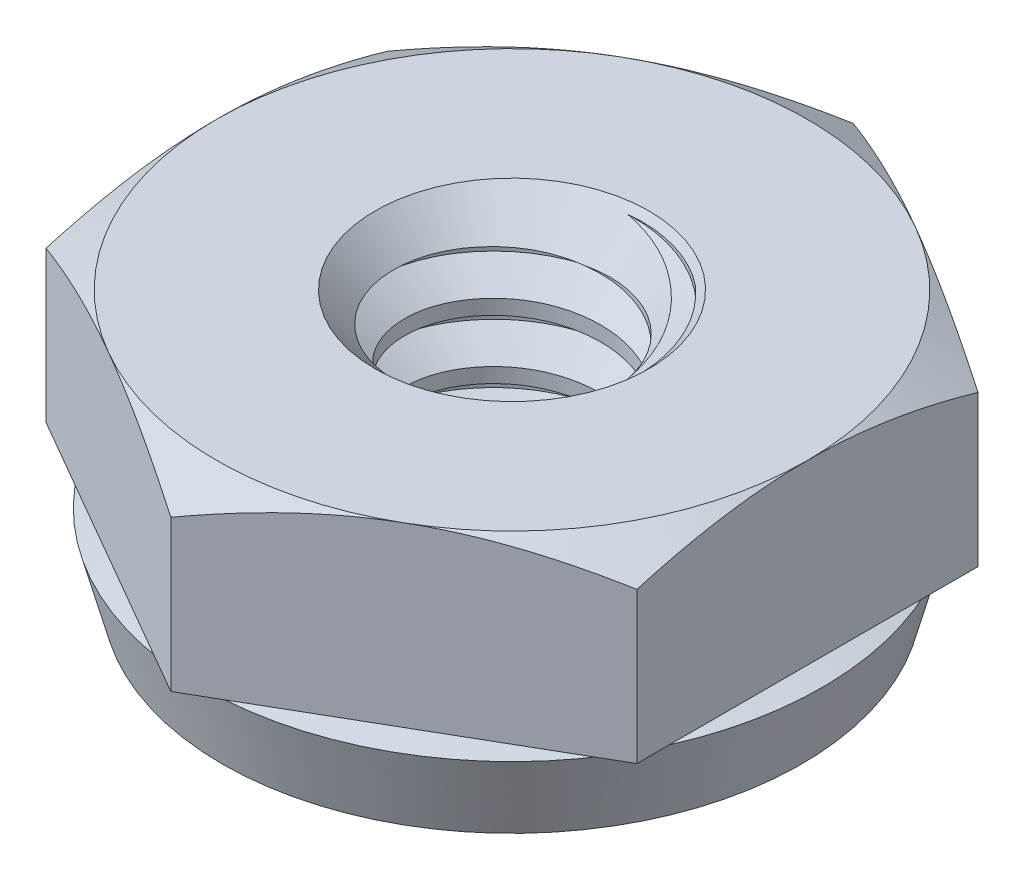
SolidWorks part; units mm, degrees
ref_plane "Front Plane" through (0, 0, 0) normal (0, 0, 1) x (1, 0, 0)
ref_plane "Top Plane" through (0, 0, 0) normal (0, 1, 0) x (1, 0, 0)
ref_plane "Right Plane" through (0, 0, 0) normal (1, 0, 0) x (0, 0, -1)
sketch "Sketch1" plane through (0, 0, 0) normal (0, 1, 0) x (1, 0, 0)
  line L1 (0, 4.5827) -> (-3.9688, 2.2914)
  line L2 (-3.9688, 2.2914) -> (-3.9688, -2.2914)
  line L3 (-3.9688, -2.2914) -> (0, -4.5827)
  line L4 (0, -4.5827) -> (3.9688, -2.2914)
  line L5 (3.9688, -2.2914) -> (3.9687, 2.2914)
  line L6 (3.9687, 2.2914) -> (0, 4.5827)
  circle A0 centre (0, 0) radius 3.9688 construction
  circle A1 centre (0, 0) radius 4.1672 construction
  point P9 (0, 4.5827)
  point P10 (0, 4.1672)
  dimension "Wd." = 7.9375
  dimension "Washer Dia." = 8.3344
extrude "Boss-Extrude1" add sketch "Sketch1" along normal blind 3.5719
sketch "Sketch4" plane through (0, 3.5719, 0) normal (0, 1, 0) x (1, 0, 0)
  circle A0 centre (0, 0) radius 1.7526
  dimension "Screw Dia." = 3.5052
sketch "Sketch5" plane through (0, 3.5719, 0) normal (0, 1, 0) x (1, 0, 0)
  circle A1 centre (0, 0) radius 1.7526
  circle A2 centre (0, 0) radius 1.7526
  point P0 (0, 1.7526)
  dimension "D1" = 0
curve "Helix/Spiral1" pitch 0.7937 height 4.3656 turns 5.5 parameters "Pitch"=0.7937
sketch "Sketch2" plane through (0, 3.5719, 0) normal (0, 1, 0) x (1, 0, 0)
  circle A0 centre (0, 0) radius 3.9688 construction
  circle A1 centre (0, 0) radius 3.9688
  point P3 (0, 3.9688)
extrude "Cut-Extrude1" cut sketch "Sketch2" against normal through all draft 60 flip side to cut
sketch "Sketch3" plane through (0, 0, 0) normal (0, -1, 0) x (1, 0, 0)
  circle A1 centre (0, 0) radius 3.9688
  circle A2 centre (0, 0) radius 3.9688
  dimension "D1" = 0
extrude "Cut-Extrude2" [suppressed] cut sketch "Sketch3" against normal through all draft 60 flip side to cut
extrude "Cut-Extrude3" cut sketch "Sketch4" against normal up to vertex (3.5719 mm away) up to point (0, 0, 0)
sketch "Sketch6" plane through (0, 0, 0) normal (1, 0, 0) x (0, 0, -1)
  line L0 (1.8385, 4.316) -> (1.8385, 3.5223) construction
  line L1 (1.8385, 3.5223) -> (1.1511, 3.9191) construction
  line L2 (1.1511, 3.9191) -> (1.8385, 4.316) construction
  line L3 (1.237, 3.9688) -> (1.237, 3.8695) construction
  line L4 (1.1511, 3.9191) -> (1.237, 3.9191) construction
  line L5 (1.7526, 4.2664) -> (1.7526, 3.5719) construction
  line L6 (1.7526, 3.9191) -> (1.8385, 3.9191) construction
  line L7 (1.7956, 4.2912) -> (1.323, 4.0184)
  line L8 (1.323, 4.0184) -> (1.323, 3.8199)
  line L9 (1.323, 3.8199) -> (1.7956, 3.5471)
  line L10 (1.7956, 3.5471) -> (1.7956, 4.2912)
  line L11 (1.237, 3.9191) -> (1.323, 3.9191) construction
  point P13 (1.7956, 3.9191)
  dimension "D1" = 0.7937
  dimension "D2" = 0.0992
sweep "Sweep1" add profiles "Sketch6" path "Helix/Spiral1"
sketch "Sketch7" plane through (0, 3.5719, 0) normal (0, 1, 0) x (1, 0, 0)
  line L0 (-1.8385, 0) -> (0, 0) construction
  circle A0 centre (0, 0) radius 1.8385
extrude "Cut-Extrude4" cut sketch "Sketch7" against normal through all draft 45 and the other way through all draft 45
sketch "Sketch8" plane through (0, 0, 0) normal (0, -1, 0) x (1, 0, 0)
  circle A1 centre (0, 0) radius 1.8385
  circle A2 centre (0, 0) radius 1.8385
  dimension "D1" = 0
extrude "Cut-Extrude5" cut sketch "Sketch8" against normal through all draft 45 and the other way through all draft 45
sketch "Sketch9" plane through (0, 0, 0) normal (1, 0, 0) x (0, 0, -1)
  line L0 (4.1672, 0) -> (-4.1672, 0) construction
  line L1 (2.9432, 0) -> (4.5827, 0)
  line L2 (0, 0) -> (0, 1.1906) construction
  line L3 (2.9432, 1.1906) -> (4.5827, 1.1906)
  line L4 (4.5827, 0) -> (4.5827, 1.1906)
  line L5 (0, 1.1906) -> (0, 3.5719) construction
  line L6 (2.9432, 1.1906) -> (2.9432, 0)
  line L7 (1.7526, 3.5719) -> (1.7526, 1.1906) construction
  line L8 (1.7526, 1.1906) -> (2.9432, 1.1906) construction
  dimension "D" = 2.3813
revolve "Cut-Revolve1" cut sketch "Sketch9" angle 360 mid plane about L2
sketch "Sketch10" plane through (0, 0, 0) normal (1, 0, 0) x (0, 0, -1)
  line L0 (2.9432, 1.1906) -> (2.9432, 0) construction
  line L1 (2.9432, 1.1906) -> (3.5658, 1.1906)
  line L2 (2.9432, 1.1906) -> (2.9432, 0.1611)
  line L3 (2.9432, 0.1611) -> (3.29, 0.1611)
  line L4 (4.1672, 1.0295) -> (3.8913, 0)
  line L5 (0, 1.1906) -> (0, 0) construction
  line L6 (4.1672, 1.0295) -> (3.5658, 1.1906)
  line L7 (3.8913, 0) -> (3.29, 0.1611)
  line L8 (3.29, 0.1611) -> (3.5658, 1.1906) construction
  line L9 (2.9432, 0) -> (4.5827, 0) construction
  dimension "D1" = 165
revolve "Revolve1" add sketch "Sketch10" angle 360 mid plane about L5
equation "\"D3@Helix/Spiral1\" = \"Pitch@Helix/Spiral1\" + \"Ht.@Boss-Extrude1\""
equation "\"D1@Sketch6\" = \"Pitch@Helix/Spiral1\""
equation "\"D2@Sketch6\" = \"D1@Sketch6\" / 8"
